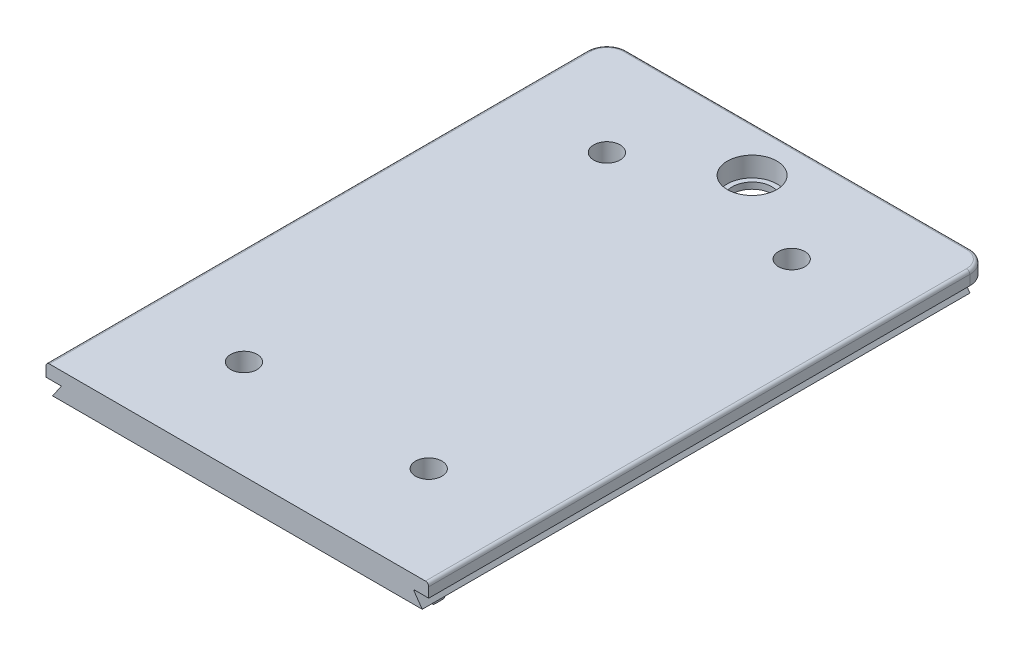
SolidWorks part; units mm, degrees
ref_plane "Front Plane" through (0, 0, 0) normal (0, 0, 1) x (1, 0, 0)
ref_plane "Top Plane" through (0, 0, 0) normal (0, 1, 0) x (1, 0, 0)
ref_plane "Right Plane" through (0, 0, 0) normal (1, 0, 0) x (0, 0, -1)
sketch "Sketch1" plane through (0, 0, 0) normal (0, 0, 1) x (1, 0, 0)
  line L0 (-29, 29) -> (-27, 29) construction
  line L1 (-29, 29) -> (-27, 29) construction
  line L2 (27, 29) -> (29, 29) construction
  line L3 (27, 29) -> (29, 29) construction
  line L4 (-27, 29) -> (-28.4004, 27)
  line L5 (-28.4004, 27) -> (28.4004, 27)
  line L6 (28.4004, 27) -> (27, 29)
  line L7 (27, 29) -> (-27, 29)
  line L8 (-27, 29) -> (-28.4004, 27) construction
  line L9 (-28.4004, 27) -> (28.4004, 27) construction
  line L10 (28.4004, 27) -> (27, 29) construction
  line L11 (27, 29) -> (-27, 29) construction
  line L12 (-26.7558, 29) -> (-28.0162, 27.2)
  line L13 (-28.0162, 27.2) -> (28.0162, 27.2)
  line L14 (28.0162, 27.2) -> (26.7558, 29)
  line L15 (-26.8362, 28.8853) -> (-28.0162, 27.2) construction
  line L16 (28.0162, 27.2) -> (26.8362, 28.8853) construction
  line L17 (26.7558, 29) -> (-26.7558, 29) construction
  line L18 (-26.7558, 29) -> (-26.7558, 29.15)
  line L19 (-26.7558, 29.15) -> (-29, 29.15)
  line L20 (-29, 29.15) -> (-29, 31.15)
  line L21 (0, 29) -> (0, 0.5) construction
  line L22 (0, 31.15) -> (0, 0.5) construction
  line L23 (-29, 31.15) -> (29, 31.15)
  line L24 (-29, 29) -> (-29, 0.5) construction
  line L25 (29, 29.15) -> (29, 31.15)
  line L26 (26.7558, 29.15) -> (29, 29.15)
  line L27 (26.7558, 29) -> (26.7558, 29.15)
  line L28 (27, 29) -> (-27, 29) construction
  dimension "D3" = 0.15
  dimension "D4" = 2
  dimension "D1" = 0
  dimension "D2" = 0.2
extrude "Boss-Extrude1" add sketch "Sketch1" against normal up to surface (83 mm away)
sketch "Sketch3" plane through (0, 0, -83) normal (0, 0, -1) x (-1, 0, 0)
  line L1 (-29, 31.15) -> (29, 31.15)
  line L2 (-29, 31.15) -> (-29, 29.15)
  line L3 (-29, 29.15) -> (29, 29.15)
  line L4 (29, 31.15) -> (29, 29.15)
extrude "Boss-Extrude2" add sketch "Sketch3" along normal up to surface (2 mm away)
fillet "Fillet1" radius 3 2 edges at (29, 30.15, -85) (-29, 30.15, -85)
sketch "Sketch4" plane through (0, 27.2, 0) normal (0, -1, 0) x (1, 0, 0)
  line L0 (28.0162, -83) -> (28.0162, 0) construction
  line L1 (28.0162, -1.5) -> (-28.0162, -1.5)
  line L2 (28.0162, -1.5) -> (28.0162, -3.5)
  line L3 (28.0162, -3.5) -> (-28.0162, -3.5)
  line L4 (-28.0162, -1.5) -> (-28.0162, -3.5)
  line L5 (-28.0162, -83) -> (-28.0162, 0) construction
  line L6 (-28.0162, 0) -> (28.0162, 0) construction
  dimension "D1" = 2
  dimension "D2" = 1.5
extrude "Boss-Extrude3" add sketch "Sketch4" along normal blind 0.25
fillet "Fillet2" radius 0.5 2 edges at (0, 26.95, -3.5) (0, 26.95, -1.5)
sketch "Sketch5" plane through (0, 31.15, 0) normal (0, 1, 0) x (1, 0, 0)
  line L0 (0, -2.31) -> (0, 2.31) construction
  line L1 (26, 85) -> (-26, 85) construction
  line L2 (0, 85) -> (0, 0) construction
  line L3 (-29, 42.5) -> (29, 42.5) construction
  line L4 (-29, 82) -> (-29, 0) construction
  circle A0 centre (0, 78) radius 3
  point P11 (0, 42.5)
  dimension "D1" = 6
  dimension "D2" = 7
extrude "Cut-Extrude1" cut sketch "Sketch5" against normal up to next
sketch "Sketch6" plane through (0, 31.15, 0) normal (0, 1, 0) x (1, 0, 0)
  circle A0 centre (0, 78) radius 3 construction
  circle A1 centre (0, 78) radius 3
  circle A2 centre (0, 78) radius 2.25
  dimension "D1" = 0.75
sketch "Sketch7" plane through (0, 31.15, 0) normal (0, 1, 0) x (1, 0, 0)
  line L0 (29, 0) -> (-29, 0) construction
  line L1 (29, 82) -> (29, 0) construction
  line L2 (29, 42.5) -> (-29, 42.5) construction
  line L4 (0, 0) -> (0, 85) construction
  line L5 (26, 85) -> (-26, 85) construction
  line L6 (-29, 82) -> (-29, 0) construction
  circle A0 centre (14, 15) radius 2
  circle A1 centre (14, 70) radius 2
  circle A2 centre (-14, 70) radius 2
  circle A3 centre (-14, 15) radius 2
  point P14 (0, 42.5)
  dimension "D1" = 4
  dimension "D2" = 15
  dimension "D3" = 15
extrude "Cut-Extrude2" cut sketch "Sketch7" against normal up to next
fillet "Fillet3" radius 0.5 5 edges at (-29, 31.15, -41) (-28.1213, 31.15, -84.1213) (0, 31.15, -85) (28.1213, 31.15, -84.1213) (29, 31.15, -41)
sketch "Sketch8" plane through (0, 31.15, 0) normal (0, 1, 0) x (1, 0, 0)
  circle A0 centre (0, 78) radius 3.75
  circle A1 centre (0, 78) radius 3 construction
  dimension "D1" = 7.5
extrude "Cut-Extrude3" cut sketch "Sketch8" against normal blind 3 contours A0
sketch "Sketch9" plane through (0, 31.15, 0) normal (0, 1, 0) x (1, 0, 0)
  line L0 (0, 0) -> (0, 85) construction
  line L1 (-24, 62) -> (24, 62)
  line L2 (-24, 62) -> (-24, 23)
  line L3 (-24, 23) -> (24, 23)
  line L4 (24, 62) -> (24, 23)
  line L7 (-26, 85) -> (26, 85) construction
  line L8 (29, 82) -> (29, 0) construction
  circle A2 centre (14, 15) radius 2 construction
  circle A3 centre (14, 70) radius 2 construction
  point P10 (0, 23)
  dimension "D1" = 8
  dimension "D2" = 8
  dimension "D3" = 5
